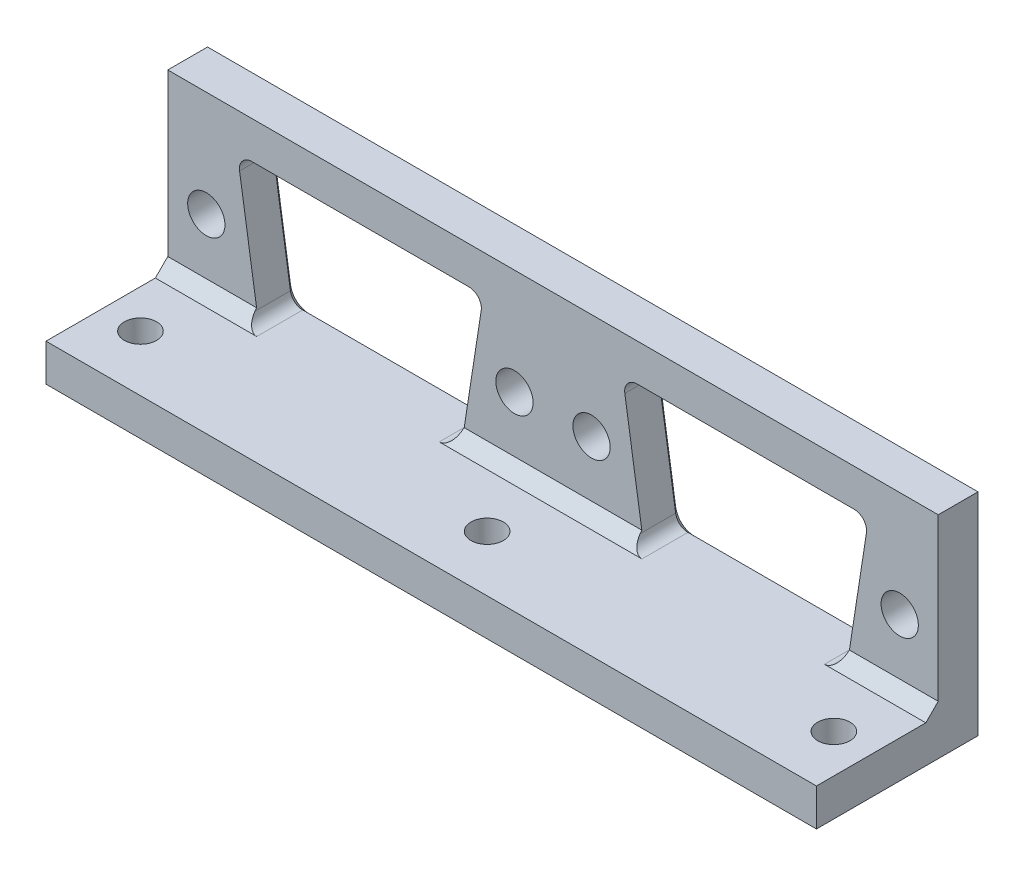
SolidWorks part; units mm, degrees
ref_plane "Front Plane" through (0, 0, 0) normal (0, 0, 1) x (1, 0, 0)
ref_plane "Top Plane" through (0, 0, 0) normal (0, 1, 0) x (1, 0, 0)
ref_plane "Right Plane" through (0, 0, 0) normal (1, 0, 0) x (0, 0, -1)
sketch "Sketch1" plane through (0, 0, 0) normal (0, 0, 1) x (1, 0, 0)
  line L0 (-31, -3) -> (31, -3)
  line L1 (0, -16.7207) -> (0, 18.3534) construction
  line L2 (7.3, 0) -> (23.7, 0)
  line L3 (5.6, 11) -> (25.4, 11)
  line L4 (-7.3, 0) -> (-23.7, 0)
  line L5 (-5.6, 11) -> (-25.4, 11)
  line L6 (-23.7, 0) -> (-25.4, 11)
  line L7 (-5.6, 11) -> (-7.3, 0)
  line L8 (5.6, 11) -> (7.3, 0)
  line L9 (25.4, 11) -> (23.7, 0)
  line L10 (-31, 14) -> (31, 14)
  line L11 (-31, 14) -> (-31, -3)
  line L12 (31, 14) -> (31, -3)
  line L13 (39.5729, 5.5) -> (-35.811, 5.5) construction
  circle A0 centre (27.9, 5.5) radius 1.5
  circle A1 centre (3.1, 5.5) radius 1.5
  circle A2 centre (-3.1, 5.5) radius 1.5
  circle A3 centre (-27.9, 5.5) radius 1.5
  point P2 (0, -3)
  point P18 (15.5, 0)
  point P19 (15.5, 11)
  point P20 (-15.5, 11)
  point P21 (-15.5, 0)
  point P30 (0, 0)
  point P31 (0, 0)
  dimension "D12" = 3
  dimension "D1" = 62
  dimension "D2" = 3
  dimension "D3" = 11
  dimension "D4" = 17
  dimension "D5" = 16.4
  dimension "D6" = 19.8
  dimension "D7" = 19.8
  dimension "D8" = 16.4
  dimension "D9" = 5.6
  dimension "D11" = 5.6
  dimension "D10" = 5.5
  dimension "D13" = 24.8
  dimension "D14" = 24.8
  dimension "D15" = 3.1
  dimension "D16" = 3.1
extrude "Boss-Extrude1" add sketch "Sketch1" along normal blind 3.2
sketch "Sketch2" plane through (0, -3, 0) normal (0, -1, 0) x (1, 0, 0)
  line L0 (-34.3715, 8.5) -> (38.2248, 8.5) construction
  line L1 (-31, 0) -> (31, 0)
  line L2 (-31, 0) -> (-31, 13)
  line L3 (-31, 13) -> (31, 13)
  line L4 (31, 0) -> (31, 13)
  circle A0 centre (0, 8.5) radius 1.3
  circle A1 centre (-27.9, 8.5) radius 1.3
  circle A2 centre (27.9, 8.5) radius 1.3
  point P14 (0, 0)
  point P16 (0, 0)
  dimension "D2" = 2.6
  dimension "D1" = 13
  dimension "D3" = 27.9
  dimension "D4" = 27.9
  dimension "D5" = 62
  dimension "D6" = 8.5
extrude "Boss-Extrude2" add sketch "Sketch2" against normal blind 3
fillet "Fillet1" radius 1 8 edges at (-25.4, 11, 1.6) (-7.3, 0, 1.6) (-23.7, 0, 1.6) (-5.6, 11, 1.6) (5.6, 11, 1.6) (7.3, 0, 1.6) (23.7, 0, 1.6) (25.4, 11, 1.6)
chamfer "Chamfer2" distance 0.5 angle 45 16 edges at (-23.4935, 0.2408, 0) (-15.5, 0, 0) (-7.5065, 0.2408, 0) (-6.4736, 5.3473, 0) (-6.0072, 10.6509, 0) (-24.5264, 5.3473, 0) (-24.9928, 10.6509, 0) (-15.5, 11, 0) (24.5264, 5.3473, 0) (15.5, 11, 0) (24.9928, 10.6509, 0) (6.0072, 10.6509, 0) (23.4935, 0.2408, 0) (6.4736, 5.3473, 0) (7.5065, 0.2408, 0) (15.5, 0, 0)
chamfer "Chamfer3" distance 1 angle 45 3 edges at (-26.9213, 0, 3.2) (26.9213, 0, 3.2) (0, 0, 3.2)
equation "\"D9@Sketch1\"= (31-19.8)/2"
equation "\"D15@Sketch1\"=(31-24.8)/2"
equation "\"D3@Sketch2\"=31 - (31-24.8)/2"
